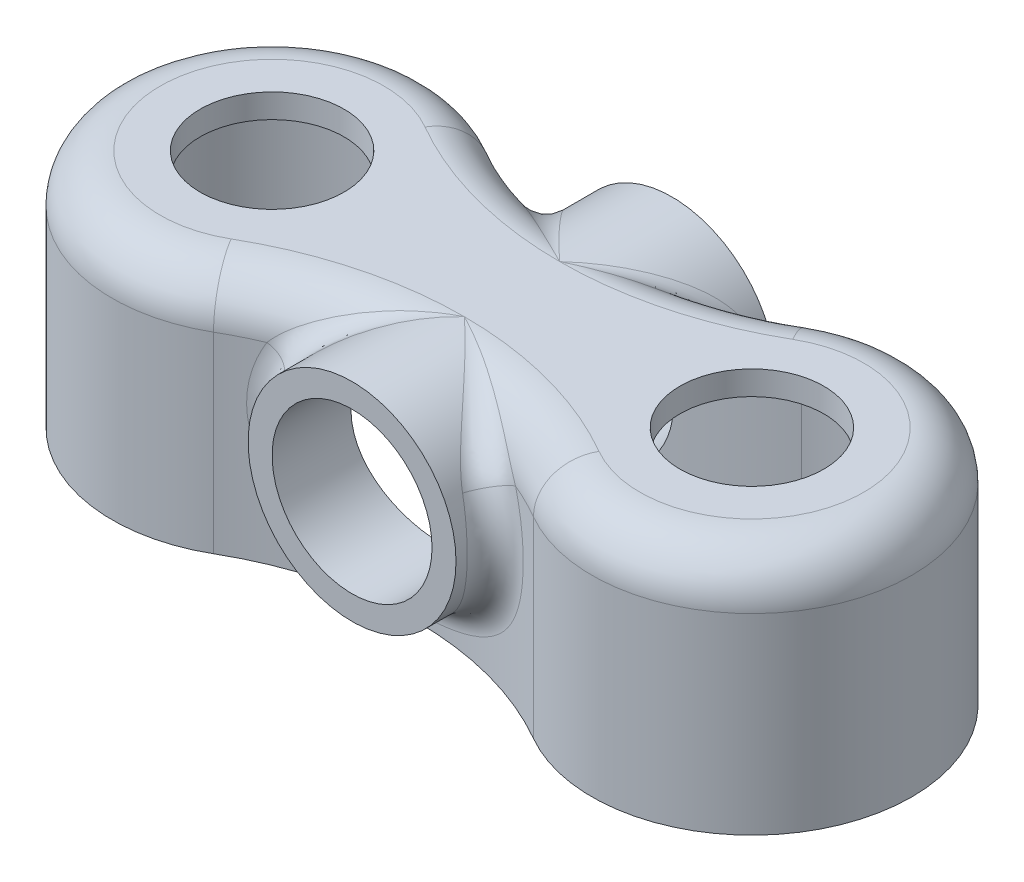
SolidWorks part; units mm, degrees
ref_plane "Front Plane" through (0, 0, 0) normal (0, 0, 1) x (1, 0, 0)
ref_plane "Top Plane" through (0, 0, 0) normal (0, 1, 0) x (1, 0, 0)
ref_plane "Right Plane" through (0, 0, 0) normal (1, 0, 0) x (0, 0, -1)
sketch "Sketch1" plane through (0, 0, 0) normal (0, 1, 0) x (1, 0, 0)
  line L0 (-30, 0) -> (30, 0) construction
  line L1 (0, 0) -> (0, 49.5738) construction
  line L2 (-20, 17.3205) -> (20, 17.3205) construction
  circle A0 centre (-30, 0) radius 9
  circle A1 centre (30, 0) radius 9
  circle A2 centre (-30, 0) radius 20
  circle A3 centre (30, 0) radius 20
  arc A4 (-20, 17.3205) -> (20, 17.3205) centre (0, 51.9615) ccw
  arc A5 (-20, -17.3205) -> (20, -17.3205) centre (0, -51.9615) cw
  point P12 (0, 0)
  dimension "D3" = 18
  dimension "D4" = 18
  dimension "D2" = 40
  dimension "D5" = 40
  dimension "D6" = 40
  dimension "D7" = 40
  dimension "D1" = 60
extrude "Boss-Extrude1" add sketch "Sketch1" along normal blind 30 contours A2 A0 | A2 A5 A3 A4 | A3 A1 | A1 | A0 region at (-30, 0, 0) region at (30, 0, 0) region at (-13.1694, 0, 9.7172) region at (0, 0, 0) region at (39.7172, 0, -16.8306)
fillet "Fillet2" radius 6 4 edges at (50, 30, 0) (0, 30, -11.9615) (0, 30, 11.9615) (-50, 30, 0)
shell "Shell2" thickness 3 removed face at (0, 0, 0)
extrude "Cut-Extrude1" cut sketch "Sketch1<3>" along normal blind 30 contours A0 | A1 region at (-30, 0, 0) region at (30, 0, 0)
sketch "Sketch1<3>" plane through (0, 0, 0) normal (0, 1, 0) x (1, 0, 0) same geometry as "Sketch1"
ref_plane "Plane1" through (0, 0, 20) normal (0, 0, 1) x (1, 0, 0)
sketch "Sketch4" plane through (0, 0, 20) normal (0, 0, 1) x (1, 0, 0)
  line L0 (-23, 30) -> (23, 30) construction
  line L1 (0, 0) -> (0, 30) construction
  circle A0 centre (0, 17) radius 13
  circle A1 centre (0, 17) radius 10
  dimension "D1" = 26
  dimension "D2" = 20
extrude "Boss-Extrude3" add sketch "Sketch4" against normal up to body
extrude "Cut-Extrude5" cut sketch "Sketch4<2>" against normal blind 15 contours A1 region at (0, 17, 20)
sketch "Sketch4<2>" plane through (0, 0, 20) normal (0, 0, 1) x (1, 0, 0) same geometry as "Sketch4"
mirror "Mirror1" about plane through (0, 0, 0) normal (0, 0, 1) of "Boss-Extrude3", "Cut-Extrude5"
fillet "Fillet3" radius 3 6 edges at (-6.3185, 28.3612, 10.5616) (8.5228, 26.8164, 12.1617) (-2.0829, 4.1679, 12.0158) (2.0829, 4.1679, -12.0158) (-6.3185, 28.3612, -10.5616) (8.5228, 26.8164, -12.1617)
